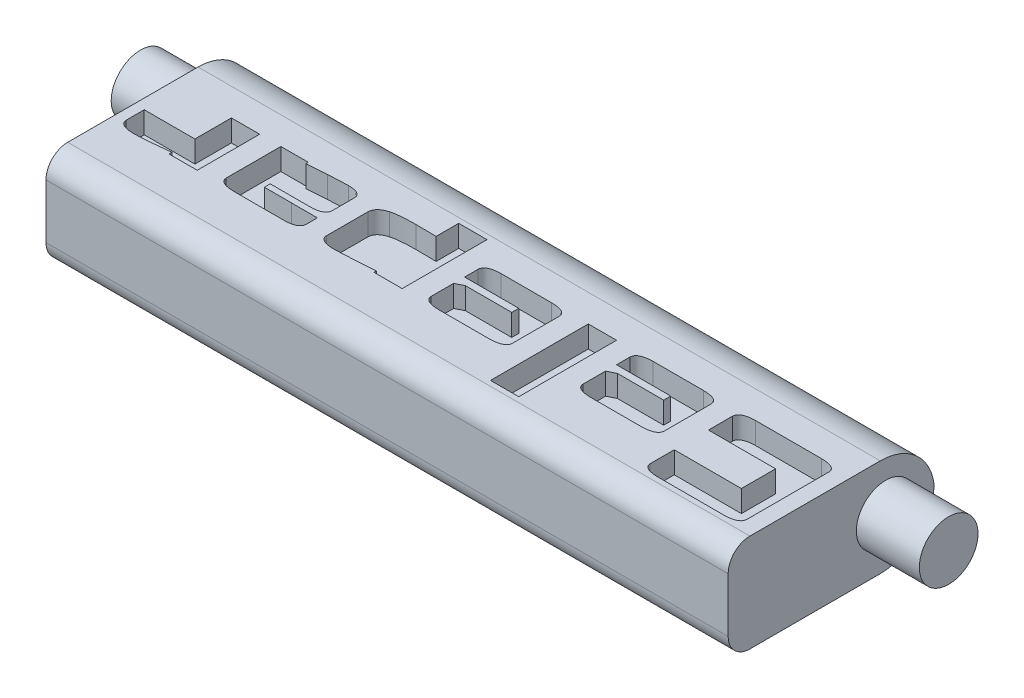
SolidWorks part; units mm, degrees
ref_plane "Front Plane" through (0, 0, 0) normal (0, 0, 1) x (1, 0, 0)
ref_plane "Top Plane" through (0, 0, 0) normal (0, 1, 0) x (1, 0, 0)
ref_plane "Right Plane" through (0, 0, 0) normal (1, 0, 0) x (0, 0, -1)
sketch "Sketch1" plane through (0, 0, 0) normal (0, 1, 0) x (1, 0, 0)
  line L1 (0, 0) -> (31.4, 0)
  line L2 (0, 0) -> (0, 9.5)
  line L3 (0, 9.5) -> (31.4, 9.5)
  line L4 (31.4, 0) -> (31.4, 9.5)
  dimension "D1" = 9.5
  dimension "D2" = 31.4
extrude "Boss-Extrude1" add sketch "Sketch1" along normal blind 4.5
sketch "Sketch2" plane through (31.4, 0, 0) normal (1, 0, 0) x (0, 0, -1)
  line L0 (9.5, 4.5) -> (9.5, 0) construction
  line L1 (0, 4.5) -> (9.5, 4.5) construction
  circle A0 centre (7.25, 2.25) radius 1.35
  dimension "D1" = 2.25
  dimension "D2" = 2.25
  dimension "D3" = 2.7
extrude "Boss-Extrude2" add sketch "Sketch2" along normal blind 2.9
sketch "Sketch3" plane through (0, 0, 0) normal (-1, 0, 0) x (0, 0, 1)
  line L0 (-9.5, 4.5) -> (-9.5, 0) construction
  line L1 (-9.5, 0) -> (0, 0) construction
  circle A0 centre (-7.25, 2.25) radius 1.35
  dimension "D1" = 2.25
  dimension "D2" = 2.7
  dimension "D3" = 2.25
extrude "Boss-Extrude3" add sketch "Sketch3" along normal blind 2.9
fillet "Fillet1" radius 1 2 edges at (15.7, 0, 0) (15.7, 4.5, 0)
fillet "Fillet2" radius 2.5 2 edges at (15.7, 0, -9.5) (15.7, 4.5, -9.5)
sketch "Sketch4" plane through (0, 4.5, 0) normal (0, 1, 0) x (1, 0, 0)
  line L0 (31.4, 5.7375) -> (0, 5.7375) construction
  line L1 (31.4, 1) -> (31.4, 7) construction
  line L2 (0, 7) -> (0, 1) construction
  line L3 (0, 9.4875) -> (31.4, 9.4875) construction
  text T0 "<b>Celepar</b>" font "Agency FB" height 4.5
  dimension "D1" = 3.75
extrude "Cut-Extrude1" cut sketch "Sketch4" against normal blind 1
sketch "Sketch5" plane through (0, 4.5, 0) normal (0, 1, 0) x (1, 0, 0)
  line L0 (29.3084, 5.1411) -> (27.5735, 5.1411) construction
  line L1 (29.3084, 1.8339) -> (27.5735, 1.8339)
  line L2 (29.3084, 1.8339) -> (29.3084, 2.7013)
  line L3 (29.3084, 2.7013) -> (27.5735, 2.7013)
  line L4 (27.5735, 1.8339) -> (27.5735, 2.7013)
  line L5 (27.5735, 4.2736) -> (29.3084, 4.2736)
  line L6 (27.5735, 4.2736) -> (27.5735, 5.1411)
  line L7 (27.5735, 5.1411) -> (29.3084, 5.1411)
  line L8 (29.3084, 4.2736) -> (29.3084, 5.1411)
  line L9 (29.3084, 1.8339) -> (29.3084, 5.1411) construction
  line L10 (17.0012, 5.2495) -> (15.7542, 5.2495) construction
  line L11 (23.9952, 4.0229) -> (22.7482, 4.0229)
  line L12 (23.9952, 4.0229) -> (23.9952, 3.3519)
  line L13 (23.9952, 3.3519) -> (22.7482, 3.3519)
  line L14 (22.7482, 4.0229) -> (22.7482, 3.3519)
  line L15 (22.7482, 4.7616) -> (23.9952, 4.7616)
  line L16 (22.7482, 4.7616) -> (22.7482, 5.2495)
  line L17 (22.7482, 5.2495) -> (23.9952, 5.2495)
  line L18 (23.9952, 4.7616) -> (23.9952, 5.2495)
  line L19 (15.7542, 4.7616) -> (17.0012, 4.7616)
  line L20 (15.7542, 4.7616) -> (15.7542, 5.2495)
  line L21 (15.7542, 5.2495) -> (17.0012, 5.2495)
  line L22 (17.0012, 4.7616) -> (17.0012, 5.2495)
  line L23 (17.0012, 4.4363) -> (17.0012, 5.2495) construction
  line L24 (6.3205, 3.3519) -> (7.5675, 3.3519) construction
  line L25 (17.0012, 4.0229) -> (15.7542, 4.0229)
  line L26 (17.0012, 4.0229) -> (17.0012, 3.3519)
  line L27 (17.0012, 3.3519) -> (15.7542, 3.3519)
  line L28 (15.7542, 4.0229) -> (15.7542, 3.3519)
  line L29 (12.2301, 3.4061) -> (10.8706, 3.4061)
  line L30 (12.2301, 3.4061) -> (12.2301, 5.2495)
  line L31 (12.2301, 5.2495) -> (10.8706, 5.2495)
  line L32 (10.8706, 3.4061) -> (10.8706, 5.2495)
  line L33 (7.5675, 4.4363) -> (6.3205, 4.4363)
  line L34 (7.5675, 4.4363) -> (7.5675, 5.371)
  line L35 (7.5675, 5.371) -> (6.3205, 5.371)
  line L36 (6.3205, 4.4363) -> (6.3205, 5.371)
  line L37 (7.5675, 3.3519) -> (6.3205, 3.3519)
  line L38 (7.5675, 3.3519) -> (7.5675, 3.7344)
  line L39 (7.5675, 3.7344) -> (6.3205, 3.7344)
  line L40 (6.3205, 3.3519) -> (6.3205, 3.7344)
  line L41 (6.3205, 4.0025) -> (6.3205, 3.3519) construction
  line L42 (2.7964, 3.4129) -> (2.7964, 5.7375) construction
  line L43 (1.7663, 3.4061) -> (2.7964, 3.4061)
  line L44 (1.7663, 3.4061) -> (1.7663, 4.0567)
  line L45 (1.7663, 4.0567) -> (2.7964, 4.0567)
  line L46 (2.7964, 3.4061) -> (2.7964, 4.0567)
extrude "Cut-Extrude2" cut sketch "Sketch5" against normal blind 1
